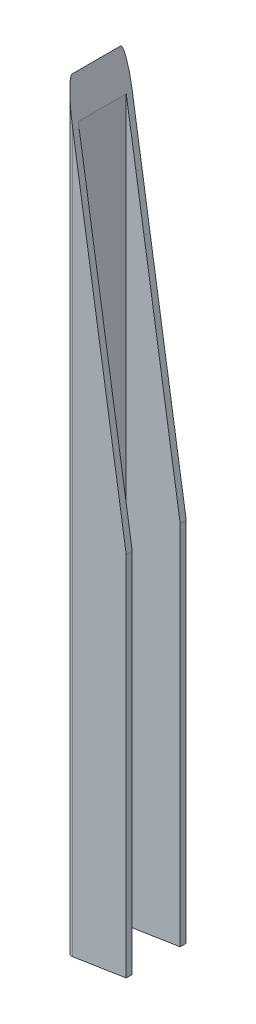
SolidWorks part; units mm, degrees
ref_plane "Спереди" through (0, 0, 0) normal (0, 0, 1) x (1, 0, 0)
ref_plane "Сверху" through (0, 0, 0) normal (0, 1, 0) x (1, 0, 0)
ref_plane "Справа" through (0, 0, 0) normal (1, 0, 0) x (0, 0, -1)
sketch "Эскиз1" plane through (0, 0, 0) normal (0, 1, 0) x (1, 0, 0)
  line L1 (-37, 15) -> (37, 15)
  line L2 (-40, 12) -> (-40, -12)
  line L3 (-37, -15) -> (37, -15)
  line L4 (40, 12) -> (40, -12)
  line L5 (-40, 15) -> (40, -15) construction
  line L6 (-40, -15) -> (40, 15) construction
  arc A0 (-37, 15) -> (-40, 12) centre (-37, 12) ccw
  arc A1 (-40, -12) -> (-37, -15) centre (-37, -12) ccw
  arc A2 (37, -15) -> (40, -12) centre (37, -12) ccw
  arc A3 (37, 15) -> (40, 12) centre (37, 12) cw
  point P0 (0, 0)
  dimension "D1" = 3
extrude "Вытянуть-Тонкостенный1" add sketch "Эскиз1" along normal blind 380 thin thin type one direction reverse wall 3
sketch "Эскиз2" plane through (0, 380, 0) normal (0, 1, 0) x (1, 0, 0)
  line L1 (-10, -21.9251) -> (41.1465, -21.9251)
  line L2 (-10, -21.9251) -> (-10, 20.9728)
  line L3 (-10, 20.9728) -> (41.1465, 20.9728)
  line L4 (41.1465, -21.9251) -> (41.1465, 20.9728)
extrude "Вырез-Вытянуть1" cut sketch "Эскиз2" against normal through all
sketch "Эскиз3" plane through (0, 0, 15) normal (0, 0, 1) x (1, 0, 0)
  line L0 (-40, 380) -> (-10, 188.0753)
  line L1 (-10, 0) -> (-10, 380) construction
  line L2 (-10, 188.0753) -> (-10, 4.6893)
  line L3 (-10, 4.6893) -> (-40, 0)
  line L4 (-40, 0) -> (-40, 380)
  line L5 (67.3818, 16.785) -> (-80.8186, -6.3804) construction
  line L6 (-10, 380) -> (-10, 0) construction
extrude "Вырез-Вытянуть2" cut sketch "Эскиз3" against normal through all flip side to cut
